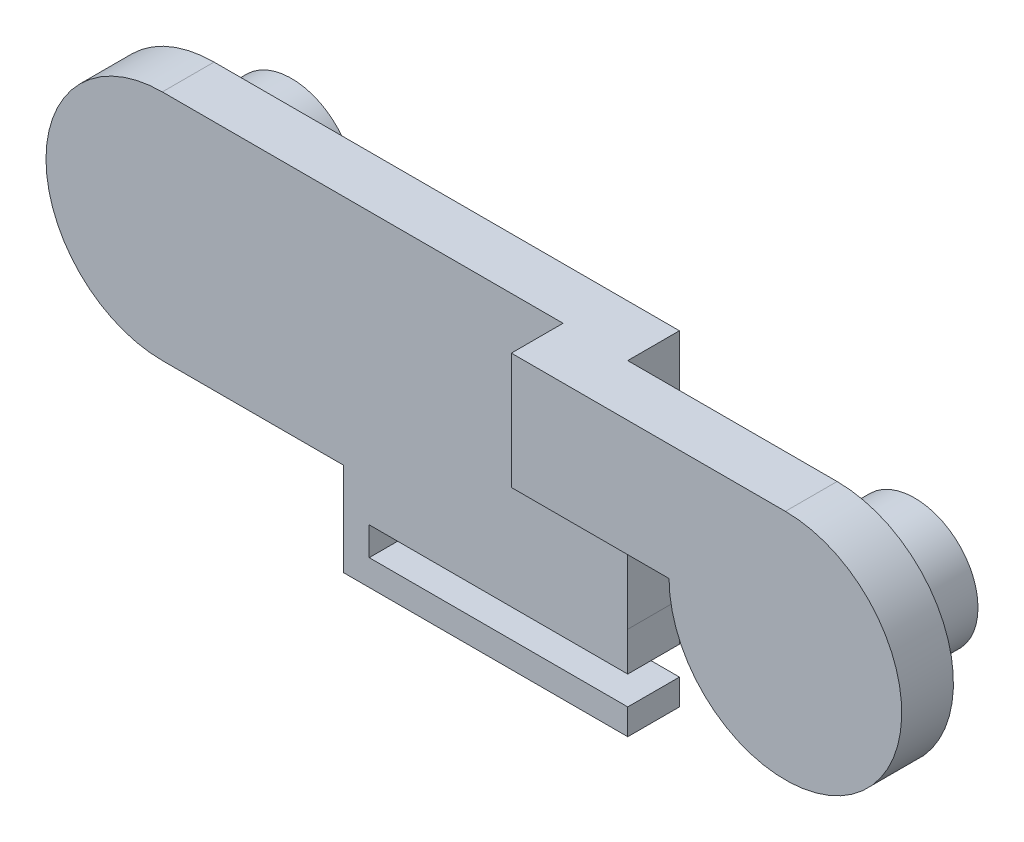
SolidWorks part; units mm, degrees
ref_plane "前视基准面" through (0, 0, 0) normal (0, 0, 1) x (1, 0, 0)
ref_plane "上视基准面" through (0, 0, 0) normal (0, 1, 0) x (1, 0, 0)
ref_plane "右视基准面" through (0, 0, 0) normal (1, 0, 0) x (0, 0, -1)
sketch "草图1" plane through (0, 0, 0) normal (0, 0, 1) x (1, 0, 0)
  line L0 (-70.4586, -12.3103) -> (-78.4607, -12.3103)
  line L18 (-56.8607, -7.8103) -> (-60.4607, -7.8103)
  line L24 (-52.3607, -3.3103) -> (-60.4607, -3.3103)
  line L25 (-60.4607, -7.8103) -> (-60.4607, -3.3103)
  line L26 (-60.4607, -3.3103) -> (-78.4607, -3.3103)
  line L27 (-60.4607, -3.3103) -> (-60.4607, -12.3103)
  line L31 (-65.4586, -13.8103) -> (-60.4586, -13.8103)
  line L32 (-70.4586, -12.3103) -> (-72.4112, -12.3103)
  line L34 (-65.4586, -13.8103) -> (-70.4586, -13.8103)
  line L36 (-70.4586, -13.8103) -> (-70.4586, -12.3103)
  line L37 (-60.4586, -13.8103) -> (-60.4607, -12.3103)
  line L39 (-70.4586, -13.8103) -> (-60.4586, -13.8103)
  line L40 (-70.4586, -13.8103) -> (-70.4586, -14.8103)
  line L41 (-70.4586, -14.8103) -> (-60.4586, -14.8103)
  line L42 (-60.4586, -13.8103) -> (-60.4586, -14.8103)
  circle A0 centre (-52.3607, -7.8103) radius 2.45
  arc A3 (-56.8607, -7.8103) -> (-52.3607, -3.3103) centre (-52.3607, -7.8103) ccw
  arc A4 (-78.4607, -3.3103) -> (-78.4607, -12.3103) centre (-78.4607, -7.8103) ccw
  circle A5 centre (-78.4607, -7.8103) radius 2.45
extrude "凸台-拉伸1" add sketch "草图1" along normal blind 2 contours L18 A3 L24 L25 A0 region at (-56.4107, -3.4652, 0)
extrude "凸台-拉伸2" add sketch "草图1<3>" against normal blind 2 separate body contours L26 A4 L0 L36 L34 L31 L37 L27 L25 A5 region at (-70.0782, -8.2249, 0)
sketch "草图1<3>" plane through (0, 0, 0) normal (0, 0, 1) x (1, 0, 0) same geometry as "草图1"
sketch "草图3" plane through (0, 0, 0) normal (0, 0, 1) x (1, 0, 0)
  line L1 (-60.4607, -3.3103) -> (-62.9607, -3.3103)
  line L2 (-60.4607, -3.3103) -> (-60.4607, -7.8103)
  line L3 (-60.4607, -7.8103) -> (-62.9607, -7.8103)
  line L4 (-62.9607, -3.3103) -> (-62.9607, -7.8103)
extrude "凸台-拉伸3" add sketch "草图3" along normal blind 2
sketch "草图4" plane through (0, 0, 0) normal (0, 0, -1) x (-1, 0, 0)
  circle A0 centre (50.4659, -9.3483) radius 0.0096
sketch "草图5" plane through (0, 0, 2) normal (0, 0, 1) x (1, 0, 0)
  circle A0 centre (-52.3607, -7.8103) radius 2.45
extrude "凸台-拉伸4" add sketch "草图5" against normal blind 5
sketch "草图7" plane through (0, 0, -2) normal (0, 0, -1) x (-1, 0, 0)
sketch "草图10" plane through (0, 0, -2) normal (0, 0, -1) x (-1, 0, 0)
  line L1 (70.4586, -12.3103) -> (71.4586, -12.3103)
  line L2 (70.4586, -12.3103) -> (70.4586, -13.8103)
  line L4 (71.4586, -12.3103) -> (71.4586, -13.8103)
  line L7 (70.4586, -13.8103) -> (70.4586, -14.9103)
  line L8 (70.4586, -15.9103) -> (71.4586, -15.9103)
  line L9 (71.4586, -13.8103) -> (71.4586, -15.9103)
  line L10 (70.4586, -15.9103) -> (60.4586, -15.9103)
  line L12 (70.4586, -14.9103) -> (60.4586, -14.9103)
  line L13 (60.4586, -15.9103) -> (60.4586, -14.9103)
extrude "凸台-拉伸8" add sketch "草图10" against normal blind 2
sketch "草图11" plane through (0, 0, -2) normal (0, 0, -1) x (-1, 0, 0)
  line L0 (70.4586, -14.9103) -> (60.4586, -14.9103) construction
  line L1 (70.4586, -13.8103) -> (69.4586, -13.8103)
  line L3 (70.4586, -14.9103) -> (69.4586, -14.9103)
  line L4 (69.4586, -13.8103) -> (69.4586, -14.9103)
  line L5 (71.4586, -15.9103) -> (71.4586, -12.3103) construction
  line L6 (70.4586, -13.8103) -> (71.4586, -13.8103)
  line L8 (70.4586, -14.9103) -> (71.4586, -14.9103)
  line L9 (71.4586, -13.8103) -> (71.4586, -14.9103)
sketch "草图13" plane through (0, 0, -2) normal (0, 0, -1) x (-1, 0, 0)
  line L1 (71.4586, -15.9103) -> (69.4586, -15.9103)
  line L2 (71.4586, -15.9103) -> (71.4586, -12.9103)
  line L3 (71.4586, -12.9103) -> (69.4586, -12.9103)
  line L4 (69.4586, -15.9103) -> (69.4586, -12.9103)
extrude "凸台-拉伸12" add sketch "草图13" along normal blind 1
sketch "草图16" plane through (0, 0, 0) normal (0, 0, 1) x (1, 0, 0)
  circle A0 centre (-78.4607, -7.8103) radius 2.45
extrude "凸台-拉伸16" add sketch "草图16" against normal blind 5
